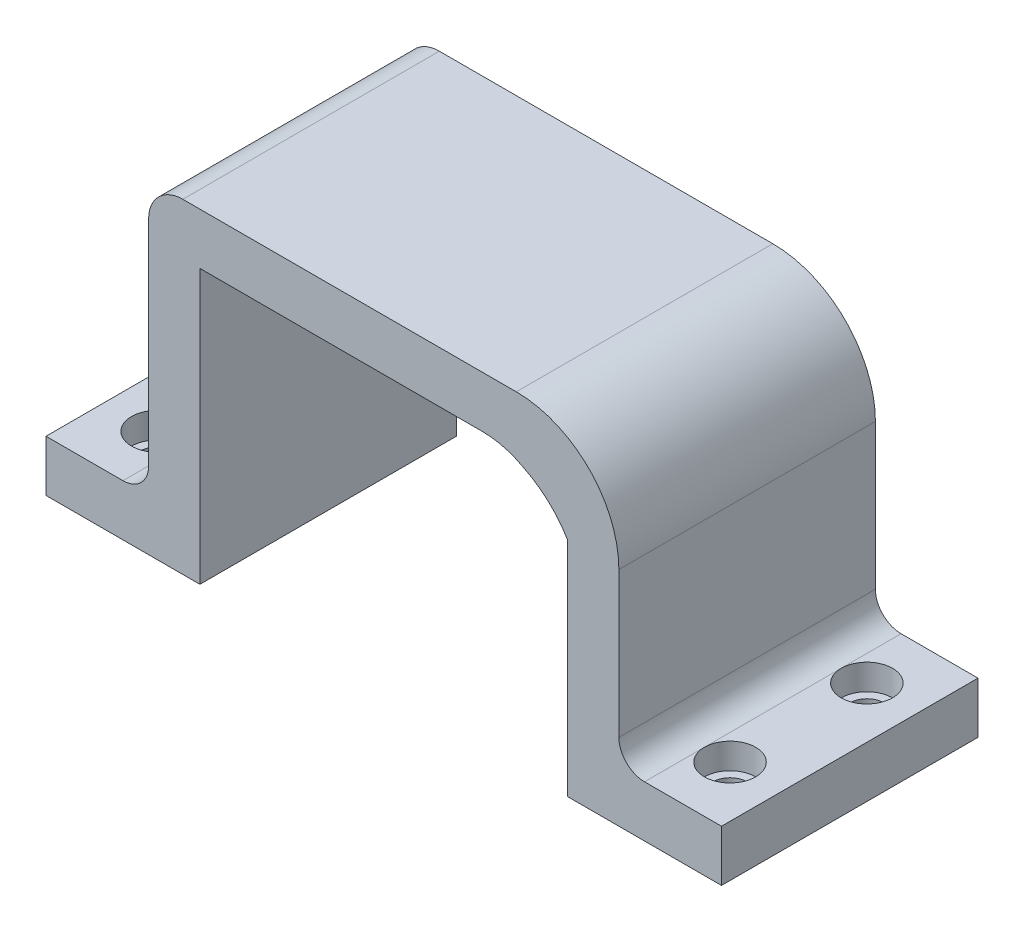
SolidWorks part; units mm, degrees
note: The reader was unsure of these and kept them because the rebuilt part matched: shared geometry of "Sketch2<3>".
ref_plane "Front Plane" through (0, 0, 0) normal (0, 0, 1) x (1, 0, 0)
ref_plane "Top Plane" through (0, 0, 0) normal (0, 1, 0) x (1, 0, 0)
ref_plane "Right Plane" through (0, 0, 0) normal (1, 0, 0) x (0, 0, -1)
sketch "Sketch1" plane through (0, 0, 0) normal (0, 0, 1) x (1, 0, 0)
  line L0 (0, 0) -> (18, 0)
  line L1 (18, 0) -> (18, 32)
  line L2 (18, 32) -> (51, 32)
  line L3 (61, 22) -> (61, 0)
  line L4 (61, 0) -> (79, 0)
  line L5 (0, 4) -> (14, 4)
  line L6 (14, 4) -> (14, 36)
  line L7 (14, 36) -> (55, 36)
  line L8 (65, 26) -> (65, 4)
  line L9 (65, 4) -> (79, 4)
  line L10 (0, 0) -> (0, 4)
  line L11 (79, 0) -> (79, 4)
  line L12 (18, 32) -> (61, 32) construction
  line L13 (61, 32) -> (61, 0) construction
  line L14 (65, 36) -> (65, 4) construction
  line L15 (14, 36) -> (65, 36) construction
  arc A0 (51, 32) -> (61, 22) centre (51, 22) cw
  arc A1 (65, 26) -> (55, 36) centre (55, 26) ccw
  point P17 (61, 32)
  dimension "D5" = 10
  dimension "D6" = 10
  dimension "D1" = 32
  dimension "D2" = 43
  dimension "D3" = 18
  dimension "D4" = 4
extrude "Boss-Extrude1" add sketch "Sketch1" along normal blind 30
sketch "Sketch4" plane through (0, 0, 30) normal (0, 0, 1) x (1, 0, 0)
  line L18 (79, 4) -> (65, 4) construction
  line L19 (65, 4) -> (65, 26) construction
  line L20 (55, 36) -> (14, 36) construction
  line L21 (14, 36) -> (14, 4) construction
  line L22 (14, 4) -> (0, 4) construction
  line L23 (79, 6) -> (67, 6)
  line L24 (67, 6) -> (67, 26)
  line L25 (55, 38) -> (12, 38)
  line L26 (12, 38) -> (12, 6)
  line L27 (12, 6) -> (0, 6)
  line L28 (79, 6) -> (67, 6)
  line L29 (67, 6) -> (67, 26)
  line L30 (55, 38) -> (12, 38)
  line L31 (12, 38) -> (12, 6)
  line L32 (12, 6) -> (0, 6)
  line L33 (79, 4) -> (65, 4)
  line L34 (65, 4) -> (65, 26)
  line L35 (55, 36) -> (14, 36)
  line L36 (14, 36) -> (14, 4)
  line L37 (14, 4) -> (0, 4)
  line L38 (0, 6) -> (0, 4)
  line L39 (79, 6) -> (79, 4)
  arc A3 (65, 26) -> (55, 36) centre (55, 26) ccw construction
  arc A4 (67, 26) -> (55, 38) centre (55, 26) ccw
  arc A5 (67, 26) -> (55, 38) centre (55, 26) ccw
  arc A6 (65, 26) -> (55, 36) centre (55, 26) ccw
  dimension "D1" = 2
extrude "Boss-Extrude2" add sketch "Sketch4" against normal up to surface (30 mm away) up to face at (41.7244, 14.5816, 0)
sketch "Sketch2"
  line L3 (0, 0) -> (12, 0) construction
  line L5 (12, -30) -> (0, -30) construction
  line L6 (79, -30) -> (67, -30) construction
  line L7 (67, 0) -> (79, 0) construction
  circle A0 centre (6, -7) radius 2
  circle A1 centre (6, -23) radius 2
  circle A2 centre (73, -7) radius 2
  circle A3 centre (73, -23) radius 2
  circle A4 centre (6, -7) radius 3
  circle A5 centre (6, -23) radius 3
  circle A6 centre (73, -7) radius 3
  circle A7 centre (73, -23) radius 3
  point P4 (6, 0)
  point P13 (73, -30)
  dimension "D2" = 4
  dimension "D4" = 4
  dimension "D7" = 6
  dimension "D1" = 7
  dimension "D3" = 7
  dimension "D5" = 7
  dimension "D6" = 7
sketch "Sketch2<3>" plane through (0, 4, 0) normal (0, 1, 0) x (1, 0, 0) same geometry as "Sketch2"
extrude "Cut-Extrude1" cut sketch "Sketch2" against normal through all and the other way through all
extrude "Cut-Extrude3" cut sketch "Sketch2<3>" along normal blind 10 from offset 1 contours A0 | A1 | A3 | A2 offset against normal yes
sketch "Sketch3" plane through (0, 0, 30) normal (0, 0, 1) x (1, 0, 0)
  line L0 (61, 22) -> (61, 26.0076)
  arc A0 (61, 26.0076) -> (51, 32) centre (50.4101, 19.6754) ccw
  arc A1 (61, 22) -> (51, 32) centre (51, 22) ccw
  arc M5 (51, 32) -> (61, 22) centre (51, 22) cw
extrude "Cut-Extrude2" cut sketch "Sketch3" against normal through all contours L0 A0 M5
fillet "Fillet1" radius 4 1 edges at (12, 38, 15)
fillet "Fillet2" radius 3 2 edges at (67, 6, 15) (12, 6, 15)
